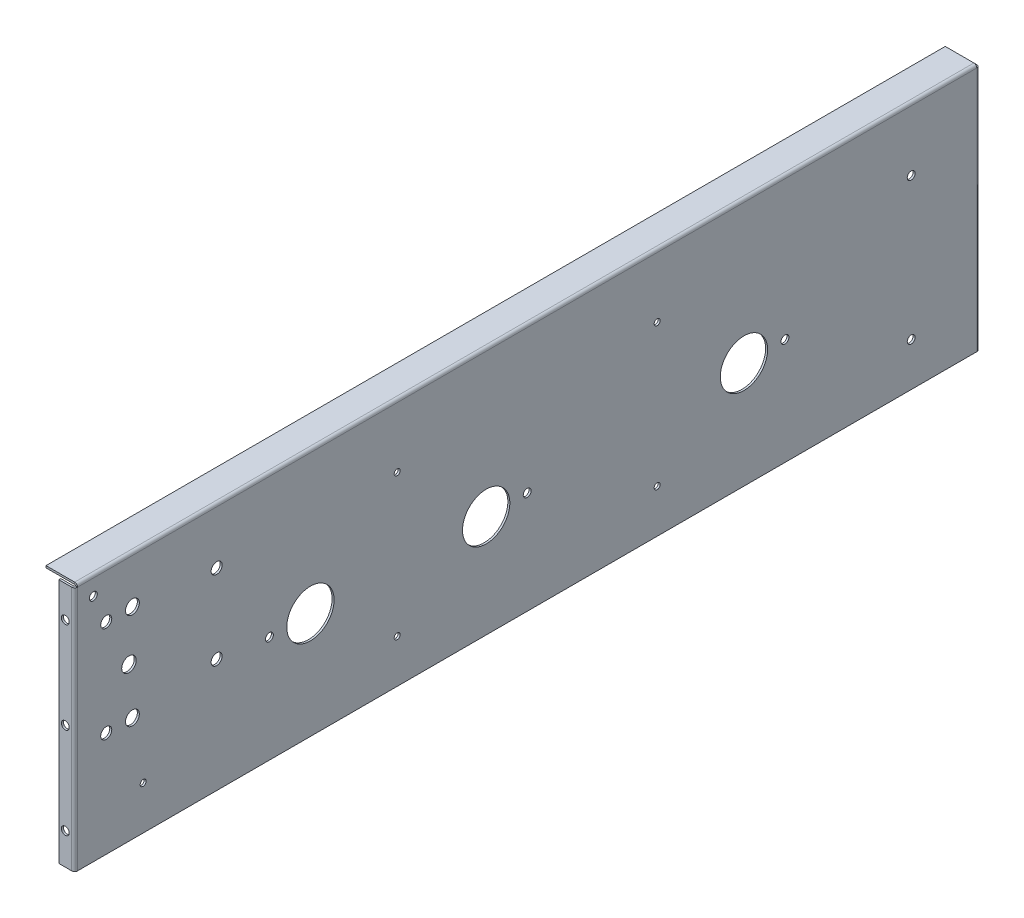
SolidWorks part; units mm, degrees
note: The reader was unsure of these and kept them because the rebuilt part matched: flange length of "Edge-Flange1", "Edge-Flange2".
ref_plane "Front Plane" through (0, 0, 0) normal (0, 0, 1) x (1, 0, 0)
ref_plane "Top Plane" through (0, 0, 0) normal (0, 1, 0) x (1, 0, 0)
ref_plane "Right Plane" through (0, 0, 0) normal (1, 0, 0) x (0, 0, -1)
sketch "Sketch1" plane through (0, 0, 0) normal (1, 0, 0) x (0, 0, -1)
  line L0 (0, -100.076) -> (0, 100.076) construction
  line L1 (-361.95, -100.076) -> (361.95, -100.076)
  line L2 (-361.95, -100.076) -> (-361.95, 100.076)
  line L3 (-361.95, 100.076) -> (361.95, 100.076)
  line L4 (361.95, -100.076) -> (361.95, 100.076)
  line L5 (-361.95, -100.076) -> (361.95, 100.076) construction
  line L6 (-361.95, 100.076) -> (361.95, -100.076) construction
  line L7 (-207.518, -14.351) -> (207.518, -14.351) construction
  line L8 (-207.518, -14.351) -> (0, -17.526) construction
  line L9 (-581.329, -119.126) -> (-428.0474, -119.126) construction
  line L10 (-119.5298, -65.151) -> (-89.7464, -65.151) construction
  line L11 (-412.75, 26.924) -> (-361.95, 26.924) construction
  line L12 (-412.75, 26.924) -> (-412.75, -100.076) construction
  line L13 (-412.75, -100.076) -> (-361.95, -100.076) construction
  line L14 (-361.95, 26.924) -> (-361.95, -100.076) construction
  line L15 (89.7464, -65.151) -> (119.5298, -65.151) construction
  line L16 (-309.118, 49.149) -> (-309.118, -65.151) construction
  line L17 (309.118, 49.149) -> (309.118, -65.151) construction
  circle A0 centre (-207.518, -14.351) radius 101.6 construction
  circle A1 centre (0, -17.526) radius 101.6 construction
  circle A2 centre (207.518, -14.351) radius 101.6 construction
  circle A3 centre (-207.518, -14.351) radius 3.175
  circle A4 centre (0, -17.526) radius 3.175
  circle A5 centre (207.518, -14.351) radius 3.175
  circle A6 centre (-104.6381, 49.149) radius 2.413
  circle A7 centre (-104.6381, -65.151) radius 2.413
  circle A8 centre (104.6381, -65.151) radius 2.413
  circle A9 centre (104.6381, 49.149) radius 2.413
  circle A10 centre (-104.6381, 49.149) radius 4.826 construction
  circle A11 centre (-104.6381, -65.151) radius 4.826 construction
  circle A12 centre (104.6381, -65.151) radius 4.826 construction
  circle A13 centre (104.6381, 49.149) radius 4.826 construction
  circle A14 centre (309.118, -65.151) radius 4.826 construction
  circle A15 centre (309.118, 49.149) radius 4.826 construction
  circle A16 centre (309.118, 49.149) radius 3.175
  circle A17 centre (309.118, -65.151) radius 3.175
  circle A19 centre (-309.118, -65.151) radius 2.413
  circle A20 centre (-309.118, -65.151) radius 4.826 construction
  point P10 (0, -14.351)
  point P14 (0, -119.126)
  point P16 (0, -100.076)
  point P35 (-104.6381, -65.151)
  point P38 (104.6381, -65.151)
  point P41 (104.6381, 49.149)
  dimension "D3" = 203.2
  dimension "D7" = 6.35
  dimension "D10" = 4.826
  dimension "D13" = 9.652
  dimension "D14" = 6.35
  dimension "D1" = 200.152
  dimension "D2" = 723.9
  dimension "D4" = 19.05
  dimension "D5" = 3.175
  dimension "D6" = 207.518
  dimension "D8" = 127
  dimension "D9" = 50.8
  dimension "D11" = 50.8
  dimension "D12" = 63.5
base flange "Base-Flange1" sketch "Sketch1" thickness 1.6002 reverse thickness direction no parameters "D1"=0.7366
edge flange "Edge-Flange1" sketch "Sketch10" flange angle 90 flange length 25.4 flange position material inside bend radius 0.7366 thickness 1.6002 relief rectangular parameters "D6"=10
sketch "Sketch10" plane through (-1.6002, 100.076, 0) normal (0, 1, 0) x (0, 0, -1)
  line L0 (361.95, 0) -> (-361.95, 0) construction
  line L1 (361.95, 0) -> (-361.95, 0)
  line L2 (-361.95, 0) -> (-361.95, 23.7998)
  line L3 (-361.95, 23.7998) -> (361.95, 23.7998)
  line L4 (361.95, 23.7998) -> (361.95, 0)
bend "EdgeBend1" bend radius 0.7366 bend angle 90 parameters "D5"=1
sketch "Sketch11" plane through (-1.6002, 0, 0) normal (-1, 0, 0) x (0, 0, 1)
  line L1 (-174.498, -14.351) -> (-207.518, -14.351) construction
  line L2 (0, -17.526) -> (33.02, -17.526) construction
  line L3 (207.518, -14.351) -> (174.498, -14.351) construction
  circle A0 centre (-174.498, -14.351) radius 19.05
  circle A1 centre (33.02, -17.526) radius 19.05
  circle A2 centre (174.498, -14.351) radius 19.05
  dimension "D1" = 38.1
  dimension "D2" = 33.02
extrude "Cut-Extrude1" cut sketch "Sketch11" against normal through all normal cut yes
sketch "Sketch23" plane through (0, 0, 0) normal (1, 0, 0) x (0, 0, -1)
  circle A0 centre (-317.7781, 62.0034) radius 5.5563
  circle A1 centre (-320.548, 23.2684) radius 5.842
  circle A2 centre (-317.7781, -15.4666) radius 5.5563
  circle A3 centre (-317.7781, 62.0034) radius 5.5563 construction
  circle A4 centre (-320.548, 23.2684) radius 5.842 construction
extrude "Cut-Extrude3" cut sketch "Sketch23" against normal up to next normal cut yes
sketch "Sketch24" plane through (0, 0, 0) normal (1, 0, 0) x (0, 0, -1)
  circle A0 centre (-338.8601, 62.0034) radius 4.445
  circle A1 centre (-338.8601, -15.4666) radius 4.445
  dimension "D1" = 8.89
extrude "Cut-Extrude4" cut sketch "Sketch24" against normal up to next normal cut yes
edge flange "Edge-Flange2" sketch "Sketch29" flange profiles "Sketch29", "Sketch30" flange angle 90 flange length 12.7 flange position bend outside bend radius 0.7366 thickness 1.6002 relief rectangular parameters "D6"=10, "D8"=0.254
sketch "Sketch29" plane through (-1.6002, 0, -361.95) normal (0, 0, -1) x (0, -1, 0)
  line L2 (-97.7392, 0) -> (-97.7392, 11.0998)
  line L3 (-97.7392, 11.0998) -> (100.076, 11.0998)
  line L4 (100.076, 11.0998) -> (100.076, 0)
  line L5 (100.076, 0) -> (-97.7392, 0) construction
  line L6 (100.076, 0) -> (-97.7392, 0)
sketch "Sketch30" plane through (-1.6002, 0, 361.95) normal (0, 0, 1) x (0, 1, 0)
  line L0 (97.7392, 0) -> (-100.076, 0) construction
  line L1 (97.7392, 0) -> (-100.076, 0)
  line L2 (-100.076, 0) -> (-100.076, 11.0998)
  line L3 (-100.076, 11.0998) -> (97.7392, 11.0998)
  line L4 (97.7392, 11.0998) -> (97.7392, 0)
bend "EdgeBend2" bend radius 0.7366 bend angle 90 parameters "D5"=2
bend "EdgeBend3" bend radius 0.7366 bend angle 90 parameters "D5"=3
sketch "Sketch34" plane through (0, 0, 364.2868) normal (0, 0, 1) x (1, 0, 0)
  line L0 (-7.5184, -100.076) -> (-7.5184, 97.7392) construction
  line L1 (-12.7, -100.076) -> (-2.3368, -100.076) construction
  line L2 (-2.3368, 97.7392) -> (-12.7, 97.7392) construction
  circle A0 centre (-7.5184, 72.3392) radius 3.175
  circle A1 centre (-7.5184, -1.1684) radius 3.175
  circle A2 centre (-7.5184, -74.676) radius 3.175
  point P12 (-7.5184, -1.1684)
  dimension "D1" = 6.35
  dimension "D2" = 25.4
  dimension "D3" = 25.4
extrude "Cut-Extrude5" cut sketch "Sketch34" against normal through all normal cut yes
sketch "Sketch35" plane through (-1.6002, 0, 0) normal (-1, 0, 0) x (0, 0, 1)
  circle A1 centre (349.25, 85.0392) radius 3.175
  dimension "D1" = 6.35
extrude "Cut-Extrude6" cut sketch "Sketch35" against normal through all normal cut yes
sketch "Sketch36" plane through (0, 0, 0) normal (1, 0, 0) x (0, 0, -1)
  circle A0 centre (-249.9601, 55.0184) radius 4.445
  circle A1 centre (-249.9601, -8.4816) radius 4.445
  circle A2 centre (-338.8601, 62.0034) radius 4.445 construction
extrude "Cut-Extrude7" cut sketch "Sketch36" against normal up to next normal cut yes
sketch "Bend-Lines1" [suppressed] plane through (0, 0, 0) normal (0, 1, 0) x (1, 0, 0)
sketch "Bounding-Box1" [suppressed] plane through (0, 0, 0) normal (0, 1, 0) x (1, 0, 0)
sheet metal parameters "Sheet-Metal1" thickness 1.6002 parameters "D1"=0.7366
flat pattern "Flat-Pattern1" [suppressed]
sketch "Bend-Lines2" plane through (0, 0, 0) normal (0, 1, 0) x (1, 0, 0)
sketch3d "Bounding-Box2" [suppressed]
  line L0 (368.3, -100.076, 0) -> (-368.3, -100.076, 0) construction
  line L1 (368.3, 100.076, 0) -> (-368.3, 100.076, 0) construction
  line L2 (368.3, -100.076, 0) -> (368.3, 100.076, 0) construction
  line L3 (-368.3, -100.076, 0) -> (-368.3, 100.076, 0) construction
sheet metal parameters "Sheet-Metal2" thickness 1.6002 parameters "D1"=0.7366
flat pattern "Flat-Pattern1"
sketch "Bend-Lines2" plane through (0, 0, 0) normal (1, 0, 0) x (0, 0, -1)
  line L0 (368.3, 98.9461) -> (-368.3, 98.9461) construction
  line L1 (368.3, 98.9461) -> (-368.3, 98.9461) construction
sketch3d "Bounding-Box2" [suppressed]
  line L0 (368.3, -100.076, 0) -> (-368.3, -100.076, 0) construction
  line L1 (368.3, 123.2162, 0) -> (-368.3, 123.2162, 0) construction
  line L2 (368.3, -100.076, 0) -> (368.3, 123.2162, 0) construction
  line L3 (-368.3, -100.076, 0) -> (-368.3, 123.2162, 0) construction
bend of the flat pattern "Flatten-<EdgeBend1>1"
sheet metal parameters "Sheet-Metal3" thickness 1.6002 parameters "D1"=0.7366
flat pattern "Flat-Pattern1"
sketch "Bend-Lines2" plane through (0, 0, 0) normal (1, 0, 0) x (0, 0, -1)
  line L0 (368.3, 98.9461) -> (-368.3, 98.9461) construction
  line L1 (368.3, 98.9461) -> (-368.3, 98.9461) construction
sketch3d "Bounding-Box2" [suppressed]
  line L0 (368.3, -100.076, 0) -> (-368.3, -100.076, 0) construction
  line L1 (368.3, 123.2162, 0) -> (-368.3, 123.2162, 0) construction
  line L2 (368.3, -100.076, 0) -> (368.3, 123.2162, 0) construction
  line L3 (-368.3, -100.076, 0) -> (-368.3, 123.2162, 0) construction
bend of the flat pattern "Flatten-<EdgeBend1>1"
sheet metal parameters "Sheet-Metal10" thickness 1.6002 parameters "D1"=0.7366
flat pattern "Flat-Pattern1"
sketch "Bend-Lines2" plane through (0, 0, 0) normal (1, 0, 0) x (0, 0, -1)
  line L0 (361.95, 98.9461) -> (-361.95, 98.9461) construction
  line L1 (361.95, 98.9461) -> (-361.95, 98.9461) construction
  line L2 (365.6969, -100.076) -> (365.6969, 97.7392) construction
  line L3 (365.6969, -100.076) -> (365.6969, 97.7392) construction
  line L4 (-365.6969, 97.7392) -> (-365.6969, -100.076) construction
  line L5 (-365.6969, 97.7392) -> (-365.6969, -100.076) construction
sketch3d "Bounding-Box2" [suppressed]
  line L0 (471.3232, -100.076, 0) -> (-471.3232, -100.076, 0) construction
  line L1 (471.3232, 123.2162, 0) -> (-471.3232, 123.2162, 0) construction
  line L2 (471.3232, -100.076, 0) -> (471.3232, 123.2162, 0) construction
  line L3 (-471.3232, -100.076, 0) -> (-471.3232, 123.2162, 0) construction
bend of the flat pattern "Flatten-<EdgeBend1>1"
sheet metal parameters "Sheet-Metal11" thickness 1.6002 parameters "D1"=0.7366
flat pattern "Flat-Pattern1"
sketch "Bend-Lines2" plane through (0, 0, 0) normal (1, 0, 0) x (0, 0, -1)
  line L0 (361.95, 98.9461) -> (-361.95, 98.9461) construction
  line L1 (361.95, 98.9461) -> (-361.95, 98.9461) construction
  point P2 (364.6809, -100.076)
  point P3 (364.6809, 97.7392)
  point P4 (-364.6809, 97.7392)
  point P5 (-364.6809, -100.076)
sketch3d "Bounding-Box2" [suppressed]
  line L0 (361.95, -100.076, 0) -> (-361.95, -100.076, 0) construction
  line L1 (361.95, 123.2162, 0) -> (-361.95, 123.2162, 0) construction
  line L2 (361.95, -100.076, 0) -> (361.95, 123.2162, 0) construction
  line L3 (-361.95, -100.076, 0) -> (-361.95, 123.2162, 0) construction
bend of the flat pattern "Flatten-<EdgeBend1>1"
sheet metal parameters "Sheet-Metal12" thickness 1.6002 parameters "D1"=0.7366
flat pattern "Flat-Pattern1"
sketch "Bend-Lines2" plane through (0, 0, 0) normal (1, 0, 0) x (0, 0, -1)
  line L0 (361.95, 98.9461) -> (-361.95, 98.9461) construction
  line L1 (361.95, 98.9461) -> (-361.95, 98.9461) construction
  line L2 (-363.1569, 97.7392) -> (-363.1569, -100.076) construction
  line L3 (363.1569, -100.076) -> (363.1569, 97.7392) construction
  line L4 (-363.1569, 97.7392) -> (-363.1569, -100.076) construction
  line L5 (363.1569, -100.076) -> (363.1569, 97.7392) construction
sketch3d "Bounding-Box2" [suppressed]
  line L0 (374.727, -100.076, 0) -> (-374.727, -100.076, 0) construction
  line L1 (374.727, 123.2162, 0) -> (-374.727, 123.2162, 0) construction
  line L2 (374.727, -100.076, 0) -> (374.727, 123.2162, 0) construction
  line L3 (-374.727, -100.076, 0) -> (-374.727, 123.2162, 0) construction
bend of the flat pattern "Flatten-<EdgeBend1>1"
bend of the flat pattern "Flatten-<EdgeBend2>1"
bend of the flat pattern "Flatten-<EdgeBend3>1"
sheet metal parameters "Sheet-Metal13" thickness 1.6002 parameters "D1"=0.7366
flat pattern "Flat-Pattern1"
sketch "Bend-Lines2" plane through (0, 0, 0) normal (1, 0, 0) x (0, 0, -1)
  line L0 (361.95, 98.9461) -> (-361.95, 98.9461) construction
  line L1 (361.95, 98.9461) -> (-361.95, 98.9461) construction
  line L2 (-363.1569, 97.7392) -> (-363.1569, -100.076) construction
  line L3 (363.1569, -100.076) -> (363.1569, 97.7392) construction
  line L4 (-363.1569, 97.7392) -> (-363.1569, -100.076) construction
  line L5 (363.1569, -100.076) -> (363.1569, 97.7392) construction
sketch3d "Bounding-Box2" [suppressed]
  line L0 (374.727, -100.076, 0) -> (-374.727, -100.076, 0) construction
  line L1 (374.727, 123.2162, 0) -> (-374.727, 123.2162, 0) construction
  line L2 (374.727, -100.076, 0) -> (374.727, 123.2162, 0) construction
  line L3 (-374.727, -100.076, 0) -> (-374.727, 123.2162, 0) construction
bend of the flat pattern "Flatten-<EdgeBend1>1"
bend of the flat pattern "Flatten-<EdgeBend2>1"
bend of the flat pattern "Flatten-<EdgeBend3>1"
sheet metal parameters "Sheet-Metal14" thickness 1.6002 parameters "D1"=0.7366
flat pattern "Flat-Pattern1"
sketch "Bend-Lines2" plane through (0, 0, 0) normal (1, 0, 0) x (0, 0, -1)
  line L0 (361.95, 98.9461) -> (-361.95, 98.9461) construction
  line L1 (361.95, 98.9461) -> (-361.95, 98.9461) construction
  line L2 (-363.1569, 97.7392) -> (-363.1569, -100.076) construction
  line L3 (363.1569, -100.076) -> (363.1569, 97.7392) construction
  line L4 (-363.1569, 97.7392) -> (-363.1569, -100.076) construction
  line L5 (363.1569, -100.076) -> (363.1569, 97.7392) construction
sketch3d "Bounding-Box2" [suppressed]
  line L0 (374.727, -100.076, 0) -> (-374.727, -100.076, 0) construction
  line L1 (374.727, 123.2162, 0) -> (-374.727, 123.2162, 0) construction
  line L2 (374.727, -100.076, 0) -> (374.727, 123.2162, 0) construction
  line L3 (-374.727, -100.076, 0) -> (-374.727, 123.2162, 0) construction
bend of the flat pattern "Flatten-<EdgeBend1>1"
bend of the flat pattern "Flatten-<EdgeBend2>1"
bend of the flat pattern "Flatten-<EdgeBend3>1"
sheet metal parameters "Sheet-Metal15" thickness 1.6002 parameters "D1"=0.7366
flat pattern "Flat-Pattern1"
sketch "Bend-Lines2" plane through (0, 0, 0) normal (1, 0, 0) x (0, 0, -1)
  line L0 (361.95, 98.9461) -> (-361.95, 98.9461) construction
  line L1 (361.95, 98.9461) -> (-361.95, 98.9461) construction
  line L2 (-363.1569, 97.7392) -> (-363.1569, -100.076) construction
  line L3 (363.1569, -100.076) -> (363.1569, 97.7392) construction
  line L4 (-363.1569, 97.7392) -> (-363.1569, -100.076) construction
  line L5 (363.1569, -100.076) -> (363.1569, 97.7392) construction
sketch3d "Bounding-Box2" [suppressed]
  line L0 (374.727, -100.076, 0) -> (-374.727, -100.076, 0) construction
  line L1 (374.727, 123.2162, 0) -> (-374.727, 123.2162, 0) construction
  line L2 (374.727, -100.076, 0) -> (374.727, 123.2162, 0) construction
  line L3 (-374.727, -100.076, 0) -> (-374.727, 123.2162, 0) construction
bend of the flat pattern "Flatten-<EdgeBend1>1"
bend of the flat pattern "Flatten-<EdgeBend2>1"
bend of the flat pattern "Flatten-<EdgeBend3>1"
